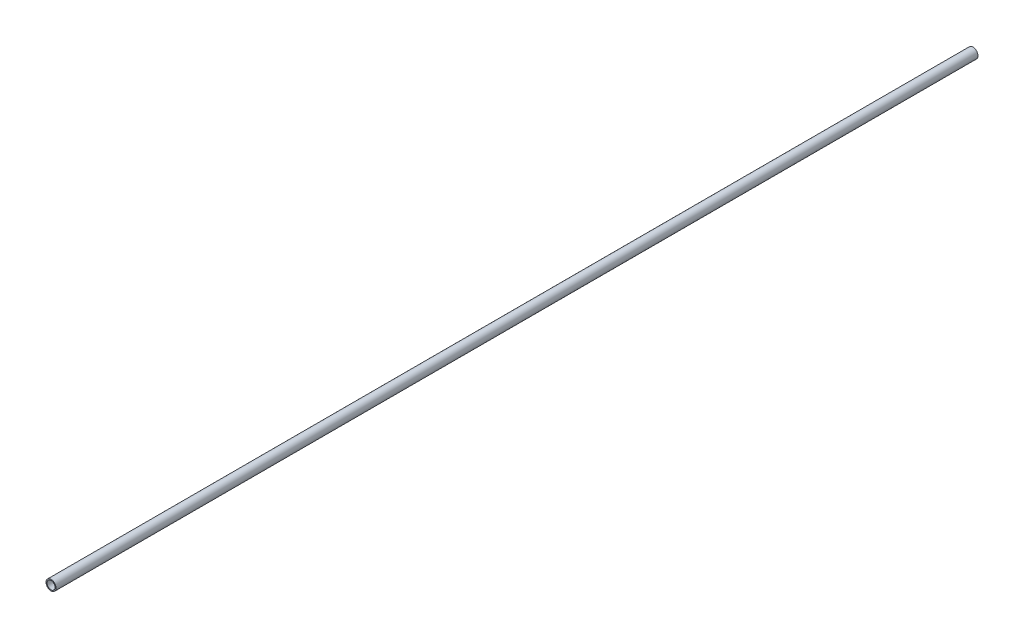
SolidWorks part; units mm, degrees
material "Thornel Mat VMA"
ref_plane "Front Plane" through (0, 0, 0) normal (0, 0, 1) x (1, 0, 0)
ref_plane "Top Plane" through (0, 0, 0) normal (0, 1, 0) x (1, 0, 0)
ref_plane "Right Plane" through (0, 0, 0) normal (1, 0, 0) x (0, 0, -1)
sketch "Sketch1" plane through (0, 0, 0) normal (0, 0, 1) x (1, 0, 0)
  circle A0 centre (0, 0) radius 5
  circle A1 centre (0, 0) radius 4
  dimension "D1" = 8
  dimension "D2" = 10
extrude "Boss-Extrude1" add sketch "Sketch1" along normal mid plane 914.4
